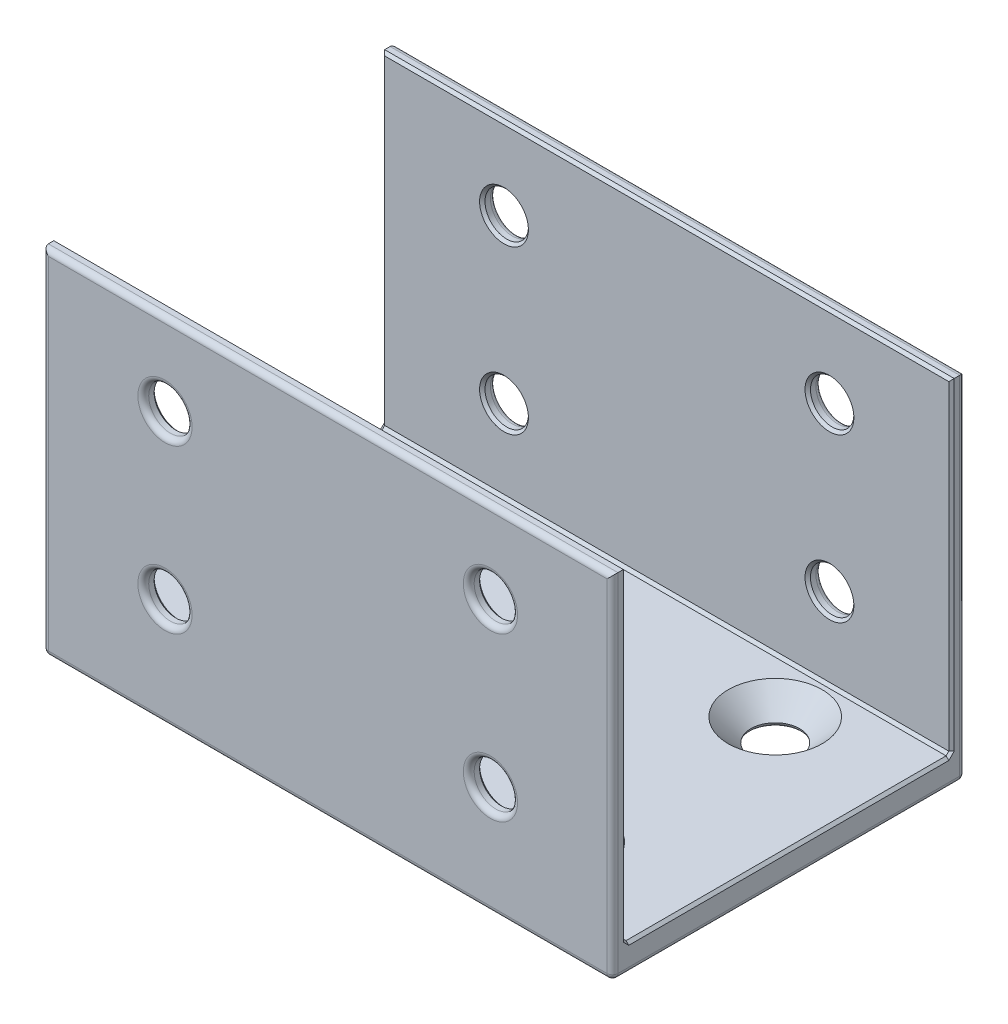
SolidWorks part; units mm, degrees
ref_plane "Płaszczyzna przednia" through (0, 0, 0) normal (0, 0, 1) x (1, 0, 0)
ref_plane "Płaszczyzna górna" through (0, 0, 0) normal (0, 1, 0) x (1, 0, 0)
ref_plane "Płaszczyzna prawa" through (0, 0, 0) normal (1, 0, 0) x (0, 0, -1)
sketch "Szkic1" plane through (0, 0, 0) normal (0, 1, 0) x (1, 0, 0)
  line L1 (52.5, -32.5) -> (-52.5, -32.5)
  line L2 (52.5, -32.5) -> (52.5, 32.5)
  line L3 (52.5, 32.5) -> (-52.5, 32.5)
  line L4 (-52.5, -32.5) -> (-52.5, 32.5)
  line L5 (52.5, -32.5) -> (-52.5, 32.5) construction
  line L6 (52.5, 32.5) -> (-52.5, -32.5) construction
  point P0 (0, 0)
  dimension "D1" = 105
  dimension "D2" = 65
extrude "Dodanie-wyciągnięcie1" add sketch "Szkic1" along normal blind 65
sketch "Szkic2" plane through (52.5, 0, 0) normal (1, 0, 0) x (0, 0, -1)
  line L1 (-30, 5) -> (30, 5)
  line L2 (-30, 5) -> (-30, 65)
  line L3 (-30, 65) -> (30, 65)
  line L4 (30, 5) -> (30, 65)
  line L5 (-30, 5) -> (30, 65) construction
  line L6 (-30, 65) -> (30, 5) construction
  line L7 (-32.5, 65) -> (32.5, 65) construction
  point P0 (0, 35)
  point P5 (0, 0)
  dimension "D1" = 60
  dimension "D2" = 60
extrude "Wytnij-wyciągnięcie1" cut sketch "Szkic2" against normal up to next
sketch "Szkic3" plane through (0, 5, 0) normal (0, 1, 0) x (1, 0, 0)
  line L0 (-82.6661, 0) -> (71.4093, 0) construction
  line L1 (0, 39.3637) -> (0, -47.3741) construction
  circle A0 centre (-30, 20) radius 4
  dimension "D1" = 8
  dimension "D2" = 40
  dimension "D3" = 60
hole_wizard "Pogłębienie stożkowe pod M8 Śrubę z łbem soczewkowym1" positions "Szkic4" profile "Szkic5" countersink size "M8" standard "ISO" end condition through all
sketch "Szkic4" plane through (0, 5, 0) normal (0, 1, 0) x (1, 0, 0)
  point P0 (-30, 20)
sketch "Szkic5" plane through (-30, 5, -20) normal (1, 0, 0) x (0, 0, 1)
  line L0 (0, 0) -> (0, 5)
  line L1 (0, 5) -> (4.5, 5)
  line L2 (4.5, 5) -> (4.5, 4.15)
  line L3 (4.5, 4.15) -> (8.65, 0)
  line L5 (8.65, 0) -> (0, 0)
  line L6 (-4.5, 4.15) -> (-8.65, 0) construction
  line L11 (0, -6.35) -> (0, 107.95) construction
  dimension "Średnica otworu na wylot" = 9
  dimension "Głębokość otworu na wylot" = 5
  dimension "Średnica zewnętrznego pogłębienia stożkowego" = 17.3
  dimension "Kąt zewnętrznego pogłębienia stożkowego" = 90
mirror "Lustro1" about plane through (0, 0, 0) normal (1, 0, 0) of "Pogłębienie stożkowe pod M8 Śrubę z łbem soczewkowym1"
mirror "Lustro2" about plane through (0, 0, 0) normal (0, 0, 1) of "Lustro1", "Pogłębienie stożkowe pod M8 Śrubę z łbem soczewkowym1"
sketch "Szkic9" plane through (0, 0, 32.5) normal (0, 0, 1) x (1, 0, 0)
  line L0 (0, 75.5156) -> (0, -11.2497) construction
  line L1 (-55.689, 35) -> (63.0524, 35) construction
  line L2 (-52.5, 0) -> (52.5, 0) construction
  circle A0 centre (-30, 50) radius 4
  circle A1 centre (30, 50) radius 4
  circle A2 centre (30, 20) radius 4
  circle A3 centre (-30, 20) radius 4
  point P11 (-29.9102, 48.1601)
  dimension "D4" = 8
  dimension "D1" = 35
  dimension "D2" = 60
  dimension "D3" = 30
hole_wizard "Otwory ustalające Ø8.0mm2" positions "Szkic10" profile "Szkic11" hole size "Ø8.0" standard "ISO" end condition through all
sketch "Szkic10" plane through (0, 0, 32.5) normal (0, 0, 1) x (1, 0, 0)
  point P0 (-30, 50)
  point P3 (30, 50)
  point P6 (30, 20)
  point P9 (-30, 20)
sketch "Szkic11" plane through (-30, 50, 32.5) normal (1, 0, 0) x (0, -1, 0)
  line L0 (0, 0) -> (0, 65)
  line L1 (0, 65) -> (4, 65)
  line L2 (4, 65) -> (4, 0)
  line L5 (4, 0) -> (0, 0)
  line L11 (0, -6.35) -> (0, 107.95) construction
  dimension "Średnica otworu na wylot" = 8
  dimension "Głębokość otworu na wylot" = 65
fillet "Zaokrąglenie1" radius 1 22 edges at (52.5, 32.5, -32.5) (0, 65, -32.5) (-52.5, 32.5, -32.5) (-26, 20, -32.5) (34, 20, -32.5) (34, 50, -32.5) (-26, 50, -32.5) (52.5, 0, 0) (0, 0, -32.5) (-52.5, 0, 0) (-30, 0, -15.5) (30, 0, -15.5) (30, 0, 24.5) (-30, 0, 24.5) (-52.5, 32.5, 32.5) (0, 65, 32.5) (52.5, 32.5, 32.5) (0, 0, 32.5) (-26, 20, 32.5) (34, 20, 32.5) (34, 50, 32.5) (-26, 50, 32.5)
chamfer "Sfazowanie1" distance 0.5 angle 45 18 edges at (0, 65, -30) (52.5, 35, -30) (0, 5, -30) (-52.5, 35, -30) (-34, 20, -30) (26, 20, -30) (26, 50, -30) (-34, 50, -30) (-52.5, 5, 0) (52.5, 5, 0) (0, 5, 30) (52.5, 35, 30) (0, 65, 30) (-52.5, 35, 30) (-26, 20, 30) (34, 20, 30) (34, 50, 30) (-26, 50, 30)
